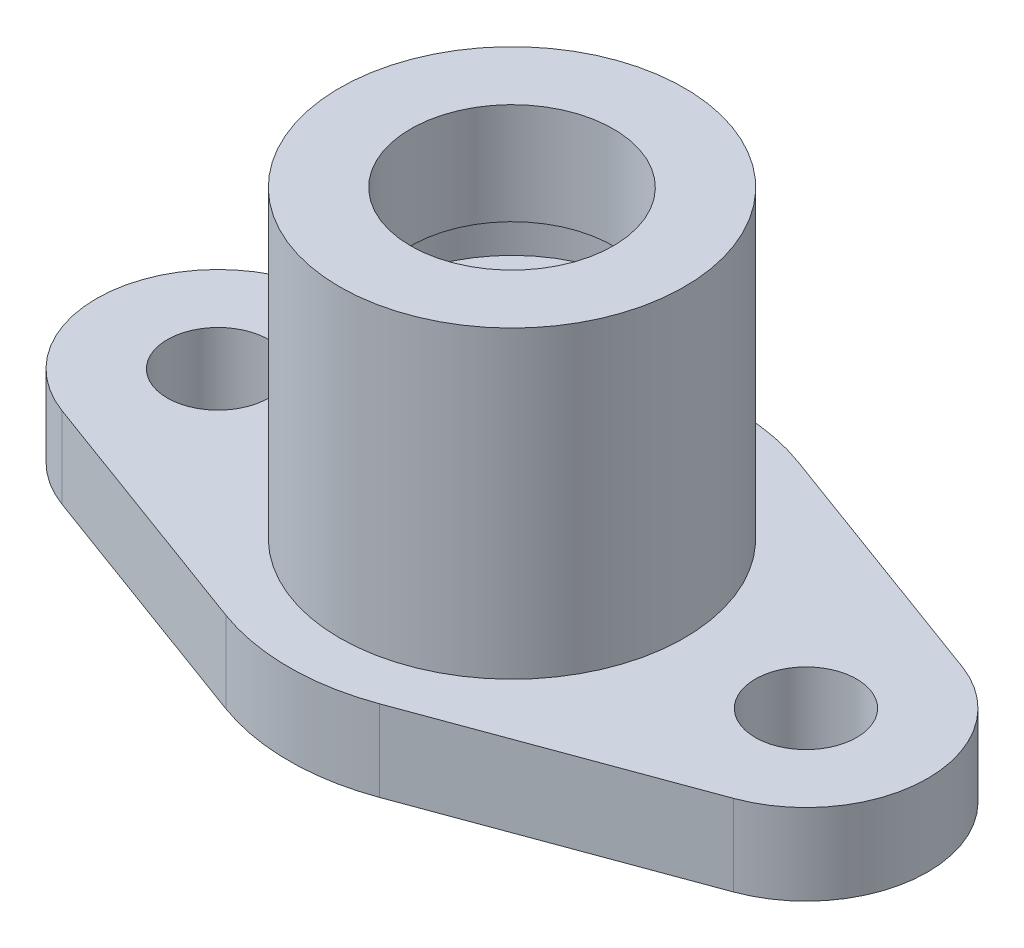
SolidWorks part; units mm, degrees
note: The reader was unsure of these and kept them because the rebuilt part matched: shared geometry of "草圖1<3>".
ref_plane "前基準面" through (0, 0, 0) normal (0, 0, 1) x (1, 0, 0)
ref_plane "上基準面" through (0, 0, 0) normal (0, 1, 0) x (1, 0, 0)
ref_plane "右基準面" through (0, 0, 0) normal (1, 0, 0) x (0, 0, -1)
sketch "草圖1" plane through (0, 0, 0) normal (0, 1, 0) x (1, 0, 0)
  line L0 (0, 0) -> (0, 33.3921) construction
  line L1 (0, 0) -> (47.6549, 0) construction
  line L2 (7.5862, 20.6507) -> (33.1379, 11.264)
  line L3 (7.5862, -20.6507) -> (33.1379, -11.264)
  line L4 (-7.5862, 20.6507) -> (-33.1379, 11.264)
  line L5 (-7.5862, -20.6507) -> (-33.1379, -11.264)
  circle A0 centre (0, 0) radius 22
  arc A1 (33.1379, -11.264) -> (33.1379, 11.264) centre (29, 0) ccw
  arc A2 (-33.1379, -11.264) -> (-33.1379, 11.264) centre (-29, 0) cw
  circle A3 centre (0, 0) radius 10
  circle A4 centre (0, 0) radius 17
  circle A5 centre (29, 0) radius 5
  circle A6 centre (-29, 0) radius 5
  dimension "D1" = 20
  dimension "D2" = 44
  dimension "D3" = 12
  dimension "D4" = 58
  dimension "D5" = 34
  dimension "D6" = 10
extrude "伸長1" add sketch "草圖1" along normal blind 8 contours L3 A1 L2 A0 A5 | A0 A4 | A4 A3 | A2 L5 A0 L4 A6
extrude "伸長2" add sketch "草圖1<3>" along normal blind 38 contours A4 A3
sketch "草圖1<3>" plane through (0, 0, 0) normal (0, 1, 0) x (1, 0, 0) same geometry as "草圖1"
sketch "草圖2" plane through (0, 0, 0) normal (0, 0, 1) x (1, 0, 0)
  line L0 (0, 0) -> (0, 43.1976) construction
  line L1 (-7.5862, 0) -> (7.5862, 0) construction
  line L3 (0, 28) -> (13, 28)
  line L4 (0, 28) -> (0, 23)
  line L5 (0, 23) -> (13, 23)
  line L6 (13, 28) -> (13, 23)
  line L7 (17, 38) -> (-17, 38) construction
  dimension "D1" = 26
  dimension "D2" = 10
  dimension "D3" = 5
revolve "除料-旋轉1" cut sketch "草圖2" angle 360 about L0
